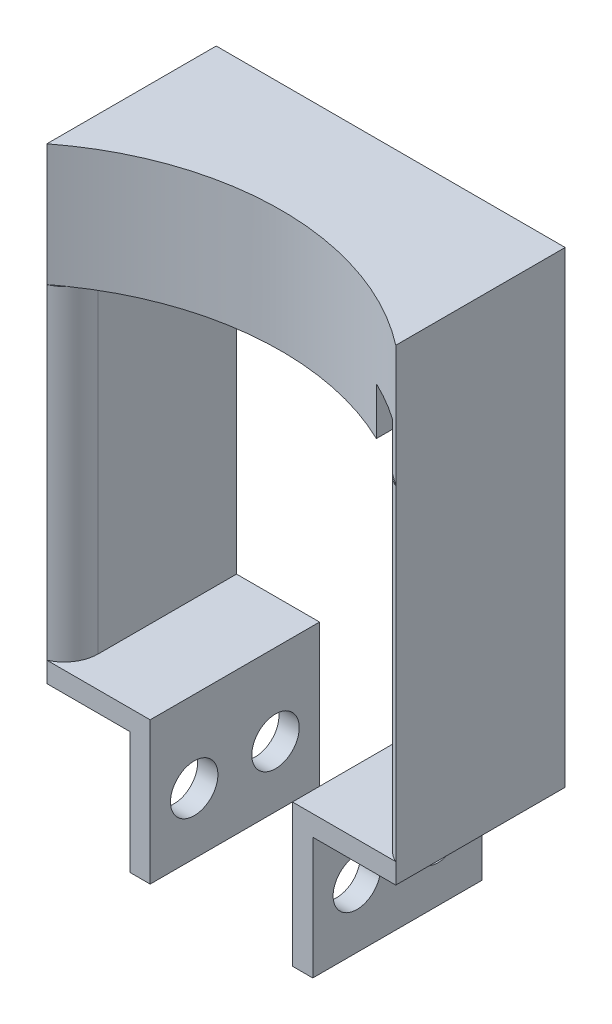
SolidWorks part; units mm, degrees
ref_plane "Front Plane" through (0, 0, 0) normal (0, 0, 1) x (1, 0, 0)
ref_plane "Top Plane" through (0, 0, 0) normal (0, 1, 0) x (1, 0, 0)
ref_plane "Right Plane" through (0, 0, 0) normal (1, 0, 0) x (0, 0, -1)
sketch "Sketch1" plane through (0, 0, 0) normal (0, 0, 1) x (1, 0, 0)
  line L0 (-20.5, 24) -> (20.5, 24)
  line L1 (20.5, 24) -> (20.5, 31)
  line L2 (20.5, 31) -> (25, 31)
  line L3 (25, 31) -> (25, -24)
  line L4 (25, -24) -> (12.75, -24)
  line L5 (-20.5, 24) -> (-20.5, -24)
  line L6 (-20.5, -24) -> (-8.25, -24)
  line L7 (-8.25, -24) -> (-8.25, -45)
  line L9 (12.75, -45) -> (12.75, -24)
  line L13 (28, 34) -> (28, -27)
  line L14 (28, -27) -> (15.75, -27)
  line L18 (-23.5, -27) -> (-11.25, -27)
  line L19 (-23.5, 27) -> (-23.5, -27)
  line L20 (-23.5, 27) -> (-23.5, 42)
  line L21 (-23.5, 42) -> (28, 42)
  line L22 (28, 42) -> (28, 34)
  line L23 (-11.25, -27) -> (-11.25, -45)
  line L24 (-23.5, 27) -> (17.5, 27) construction
  line L25 (17.5, 34) -> (28, 34) construction
  line L26 (17.5, 27) -> (17.5, 34) construction
  line L27 (-11.25, -48) -> (15.75, -48) construction
  line L28 (-8.25, -45) -> (12.75, -45) construction
  line L29 (15.75, -48) -> (15.75, -27) construction
  line L30 (-11.25, -27) -> (-11.25, -48) construction
  line L31 (-11.25, -45) -> (-8.25, -45)
  line L32 (15.75, -27) -> (15.75, -45)
  line L33 (15.75, -45) -> (12.75, -45)
  point P10 (-20.5, 0)
  point P12 (0, 24)
  dimension "D1" = 41
  dimension "D2" = 55
  dimension "D3" = 4.5
  dimension "D4" = 48
  dimension "D5" = 21
  dimension "D6" = 21
  dimension "D7" = 3
  dimension "D8" = 15
extrude "Boss-Extrude1" add sketch "Sketch1" along normal blind 25
sketch "Sketch2" plane through (-11.25, 0, 0) normal (1, 0, 0) x (0, 0, -1)
  line L0 (-12.5, -27) -> (-12.5, -45) construction
  line L3 (-25, -45) -> (0, -45) construction
  line L4 (-25, -27) -> (0, -27) construction
  line L5 (-25, -27) -> (0, -27) construction
  circle A0 centre (-6.5, -36) radius 3.5
  circle A1 centre (-18.5, -36) radius 3.5
  point P0 (-18.5, -36)
  point P5 (-12.5, -48)
  point P8 (-12.5, -27)
  point P11 (-12.5, -45)
  dimension "D1" = 7
  dimension "D2" = 9
  dimension "D3" = 6
extrude "Cut-Extrude1" cut sketch "Sketch2" along normal through all
sketch "Sketch4" plane through (0, 42, 0) normal (0, 1, 0) x (1, 0, 0)
  line L0 (28, -25) -> (-23.5, -25)
  arc A0 (-23.5, -25) -> (28, -25) centre (2.25, -58.1804) cw
  dimension "D1" = 42
extrude "Cut-Extrude3" cut sketch "Sketch4" against normal up to surface (18 mm away) up to face at (0, 24, 12.5)
fillet "Fillet1" radius 5 2 edges at (25, 0, 25) (-20.5, 0, 25)
